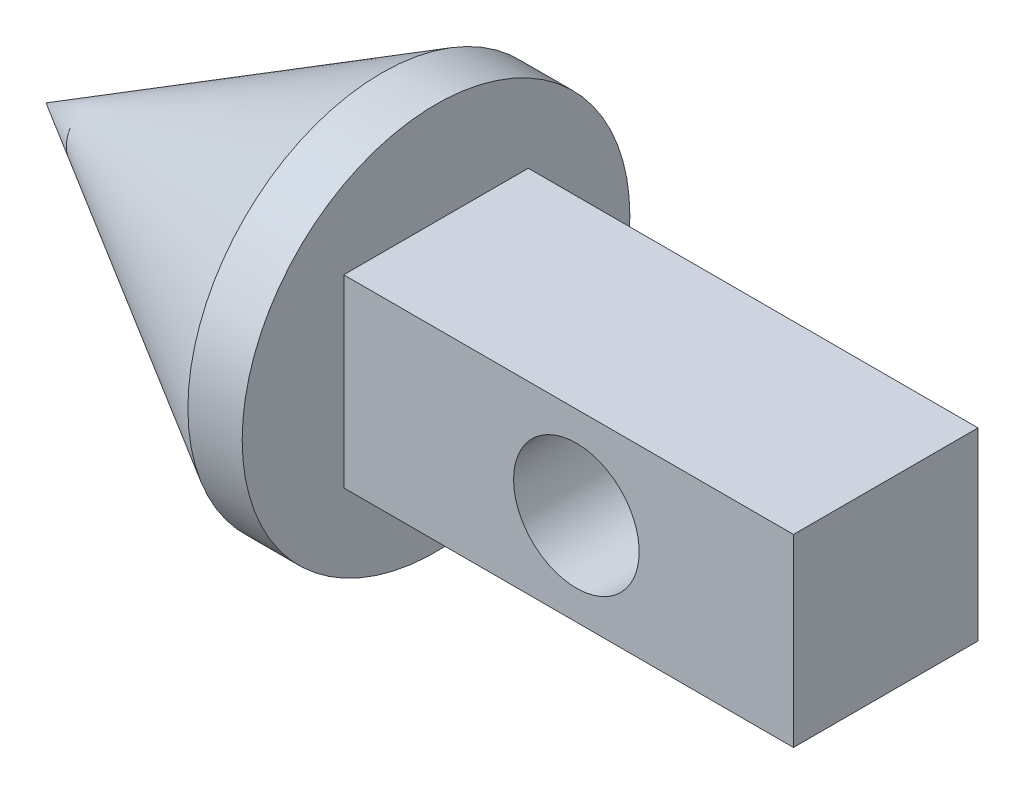
SolidWorks part; units mm, degrees
material "PLA"
ref_plane "Front Plane" through (0, 0, 0) normal (0, 0, 1) x (1, 0, 0)
ref_plane "Top Plane" through (0, 0, 0) normal (0, 1, 0) x (1, 0, 0)
ref_plane "Right Plane" through (0, 0, 0) normal (1, 0, 0) x (0, 0, -1)
sketch "Sketch1" plane through (0, 0, 0) normal (1, 0, 0) x (0, 0, -1)
  line L1 (-5.95, -5.95) -> (5.95, -5.95)
  line L2 (-5.95, -5.95) -> (-5.95, 5.95)
  line L3 (-5.95, 5.95) -> (5.95, 5.95)
  line L4 (5.95, -5.95) -> (5.95, 5.95)
  line L5 (-5.95, -5.95) -> (5.95, 5.95) construction
  line L6 (-5.95, 5.95) -> (5.95, -5.95) construction
  point P0 (0, 0)
  dimension "D1" = 11.9
  dimension "D2" = 11.9
extrude "Boss-Extrude1" add sketch "Sketch1" along normal blind 29
sketch "Sketch2" plane through (0, 0, 5.95) normal (0, 0, 1) x (1, 0, 0)
  line L0 (0, 0) -> (15, 0) construction
  circle A0 centre (15, 0) radius 4.05
  dimension "D2" = 8.1
  dimension "D1" = 15
extrude "Cut-Extrude1" cut sketch "Sketch2" against normal up to next and the other way through all
sketch "Sketch3" plane through (0, 0, 0) normal (-1, 0, 0) x (0, 0, 1)
  circle A0 centre (0, 0) radius 12.5
  dimension "D1" = 25
extrude "Boss-Extrude2" add sketch "Sketch3" along normal blind 3.5
sketch "Sketch4" plane through (0, 0, 0) normal (0, 0, 1) x (1, 0, 0)
  line L0 (0, 0) -> (-25.1506, 0) construction
  line L1 (-3.5, 0) -> (-3.5, 12.5)
  line L2 (-3.5, 12.5) -> (-3.5, -12.5) construction
  line L3 (-3.5, 12.5) -> (-25.1506, 0)
  line L4 (-25.1506, 0) -> (-3.5, 0)
  dimension "D1" = 30
revolve "Revolve1" add sketch "Sketch4" angle 360 about L0
ref_axis "Axis1" through (-35.675, 0, 0) along (1, 0, 0)
